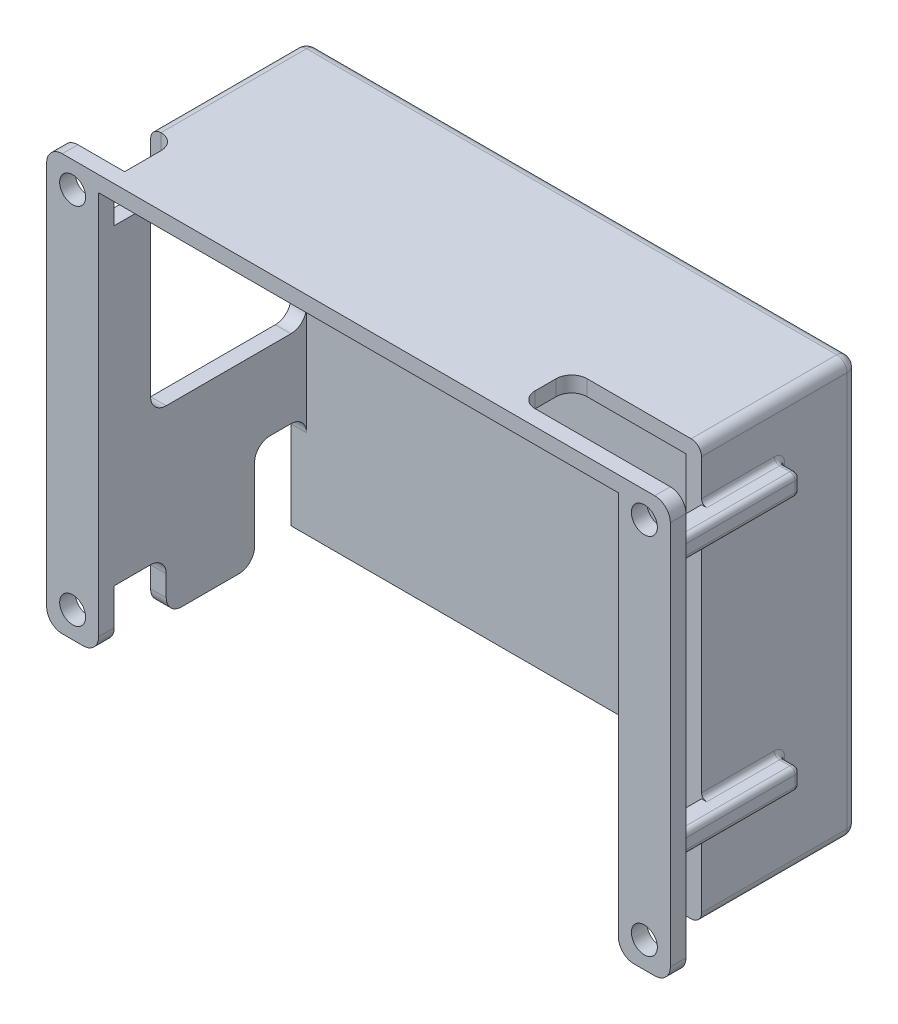
SolidWorks part; units mm, degrees
ref_plane "Front Plane" through (0, 0, 0) normal (0, 0, 1) x (1, 0, 0)
ref_plane "Top Plane" through (0, 0, 0) normal (0, 1, 0) x (1, 0, 0)
ref_plane "Right Plane" through (0, 0, 0) normal (1, 0, 0) x (0, 0, -1)
sketch "Sketch2" plane through (0, 0, 0) normal (0, 0, 1) x (1, 0, 0)
  line L1 (15.306, 62.8336) -> (75.306, 62.8336)
  line L2 (15.306, 62.8336) -> (15.306, 22.8336)
  line L3 (15.306, 22.8336) -> (75.306, 22.8336)
  line L4 (75.306, 62.8336) -> (75.306, 22.8336)
  circle A0 centre (17.806, 60.3336) radius 1.25
  circle A1 centre (17.806, 25.3336) radius 1.25
  circle A2 centre (72.806, 25.3336) radius 1.25
  circle A3 centre (72.806, 60.3336) radius 1.25
  dimension "D2" = 2.5
  dimension "D1" = 60
  dimension "D3" = 40
  dimension "D4" = 2.5
  dimension "D5" = 2.5
  dimension "D6" = 2.5
  dimension "D7" = 2.5
extrude "Boss-Extrude3" add sketch "Sketch2" along normal blind 1.5
sketch "Sketch3" plane through (0, 0, 0) normal (0, 0, -1) x (-1, 0, 0)
  line L0 (-75.306, 62.8336) -> (-15.306, 62.8336) construction
  line L1 (-71.806, 62.8336) -> (-18.806, 62.8336)
  line L2 (-71.806, 62.8336) -> (-71.806, 22.8336)
  line L3 (-71.806, 22.8336) -> (-18.806, 22.8336)
  line L4 (-18.806, 62.8336) -> (-18.806, 22.8336)
  line L6 (-15.306, 22.8336) -> (-75.306, 22.8336) construction
  line L7 (-75.306, 22.8336) -> (-75.306, 62.8336) construction
  line L8 (-15.306, 62.8336) -> (-15.306, 22.8336) construction
  dimension "D1" = 0
  dimension "D2" = 0
  dimension "D3" = 3.5
  dimension "D4" = 3.5
extrude "Boss-Extrude4" add sketch "Sketch3" along normal blind 20
sketch "Sketch7" plane through (0, 0, 1.5) normal (0, 0, 1) x (1, 0, 0)
  line L0 (75.306, 62.8336) -> (15.306, 62.8336) construction
  line L1 (20.306, 61.3336) -> (70.306, 61.3336)
  line L2 (20.306, 61.3336) -> (20.306, 22.8336)
  line L3 (20.306, 22.8336) -> (70.306, 22.8336)
  line L4 (70.306, 61.3336) -> (70.306, 22.8336)
  line L5 (15.306, 62.8336) -> (15.306, 22.8336) construction
  line L6 (75.306, 22.8336) -> (75.306, 62.8336) construction
  line L7 (15.306, 22.8336) -> (75.306, 22.8336) construction
  dimension "D1" = 1.5
  dimension "D2" = 5
  dimension "D3" = 5
  dimension "D4" = 0
extrude "Cut-Extrude4" cut sketch "Sketch7" against normal blind 20
sketch "Sketch8" plane through (71.806, 0, 0) normal (1, 0, 0) x (0, 0, -1)
  line L0 (20, 62.8336) -> (0, 62.8336) construction
  line L1 (0, 62.8336) -> (5, 62.8336)
  line L2 (0, 62.8336) -> (0, 22.8336)
  line L3 (0, 22.8336) -> (5, 22.8336)
  line L4 (5, 62.8336) -> (5, 22.8336)
  line L5 (20, 22.8336) -> (0, 22.8336) construction
  line L6 (0, 24.5836) -> (0, 22.8336) construction
  dimension "D2" = 5
extrude "Cut-Extrude5" cut sketch "Sketch8" against normal blind 12.5
sketch "Sketch11" plane through (18.806, 0, 0) normal (-1, 0, 0) x (0, 0, 1)
  line L1 (0, 62.8336) -> (-5, 62.8336)
  line L2 (0, 62.8336) -> (0, 57.8336)
  line L3 (0, 57.8336) -> (-5, 57.8336)
  line L4 (-5, 62.8336) -> (-5, 57.8336)
  line L5 (0, 22.8336) -> (-5, 22.8336)
  line L6 (0, 22.8336) -> (0, 27.8336)
  line L7 (0, 27.8336) -> (-5, 27.8336)
  line L8 (-5, 22.8336) -> (-5, 27.8336)
  dimension "D1" = 5
  dimension "D2" = 5
extrude "Cut-Extrude8" cut sketch "Sketch11" against normal blind 2.5
sketch "Sketch17" plane through (18.806, 0, 0) normal (-1, 0, 0) x (0, 0, 1)
  line L0 (-20, 22.8336) -> (-20, 62.8336) construction
  line L1 (-18.5, 40.3336) -> (-3.5, 40.3336)
  line L2 (-18.5, 40.3336) -> (-18.5, 57.8336)
  line L3 (-18.5, 57.8336) -> (-3.5, 57.8336)
  line L4 (-3.5, 40.3336) -> (-3.5, 57.8336)
  line L5 (-20, 22.8336) -> (-5, 22.8336) construction
  line L6 (1.5, 62.8336) -> (0, 62.8336) construction
  line L7 (-18.5, 22.8336) -> (-13.5, 22.8336)
  line L8 (-18.5, 22.8336) -> (-18.5, 32.8336)
  line L9 (-18.5, 32.8336) -> (-13.5, 32.8336)
  line L10 (-13.5, 22.8336) -> (-13.5, 32.8336)
  dimension "D1" = 5
  dimension "D2" = 17.5
  dimension "D3" = 15
  dimension "D4" = 1.5
  dimension "D5" = 10
  dimension "D6" = 1.5
  dimension "D7" = 5
extrude "Cut-Extrude13" cut sketch "Sketch17" against normal blind 2.5
sketch "Sketch19" plane through (0, 0, 0) normal (0, 0, -1) x (-1, 0, 0)
  line L0 (-70.306, 61.3336) -> (-70.306, 22.8336) construction
  line L1 (-71.806, 33.3336) -> (-73.806, 33.3336)
  line L2 (-71.806, 33.3336) -> (-71.806, 31.3336)
  line L3 (-71.806, 31.3336) -> (-73.806, 31.3336)
  line L4 (-73.806, 33.3336) -> (-73.806, 31.3336)
  line L5 (-70.306, 22.8336) -> (-75.306, 22.8336) construction
  line L6 (-75.306, 62.8336) -> (-59.306, 62.8336) construction
  line L7 (-71.806, 57.8336) -> (-73.806, 57.8336)
  line L8 (-71.806, 57.8336) -> (-71.806, 55.8336)
  line L9 (-71.806, 55.8336) -> (-73.806, 55.8336)
  line L10 (-73.806, 57.8336) -> (-73.806, 55.8336)
  dimension "D1" = 1.5
  dimension "D2" = 2
  dimension "D3" = 8.5
  dimension "D4" = 2
  dimension "D5" = 5
extrude "Boss-Extrude5" add sketch "Sketch19" along normal blind 12.5
fillet "Fillet1" radius 1.5 6 edges at (15.306, 22.8336, 0.75) (20.306, 22.8336, 0.75) (15.306, 62.8336, 0.75) (75.306, 62.8336, 0.75) (75.306, 22.8336, 0.75) (70.306, 22.8336, 0.75)
fillet "Fillet2" radius 1.5 12 edges at (59.306, 62.0836, -5) (59.306, 62.0836, 0) (19.556, 40.3336, -3.5) (19.556, 40.3336, -18.5) (19.556, 57.8336, -3.5) (19.556, 57.8336, -5) (19.556, 57.8336, -18.5) (19.556, 32.8336, -18.5) (19.556, 32.8336, -13.5) (19.556, 22.8336, -13.5) (19.556, 22.8336, -5) (19.556, 27.8336, -5)
fillet "Fillet3" radius 1 7 edges at (45.306, 62.8336, -20) (18.806, 42.8336, -20) (45.306, 22.8336, -20) (71.806, 42.8336, -20) (71.806, 22.8336, -12.5) (18.806, 62.8336, -12.5) (71.806, 62.8336, -12.5)
fillet "Fillet4" radius 0.5 24 edges at (72.806, 55.8336, 0) (72.806, 33.3336, 0) (72.806, 31.3336, 0) (73.806, 56.8336, 0) (71.806, 32.3336, 0) (73.806, 32.3336, 0) (71.806, 56.8336, 0) (72.806, 57.8336, 0) (71.806, 32.3336, -12.5) (71.806, 56.8336, -12.5) (71.806, 33.3336, -8.75) (71.806, 57.8336, -8.75) (71.806, 55.8336, -8.75) (73.806, 57.8336, -6.25) (73.806, 33.3336, -6.25) (71.806, 31.3336, -8.75) (73.806, 31.3336, -6.25) (73.806, 55.8336, -6.25) (72.806, 55.8336, -12.5) (73.806, 56.8336, -12.5) (72.806, 57.8336, -12.5) (72.806, 31.3336, -12.5) (73.806, 32.3336, -12.5) (72.806, 33.3336, -12.5)
fillet "Fillet5" radius 1.5 1 edges at (21.306, 62.0836, -5)
